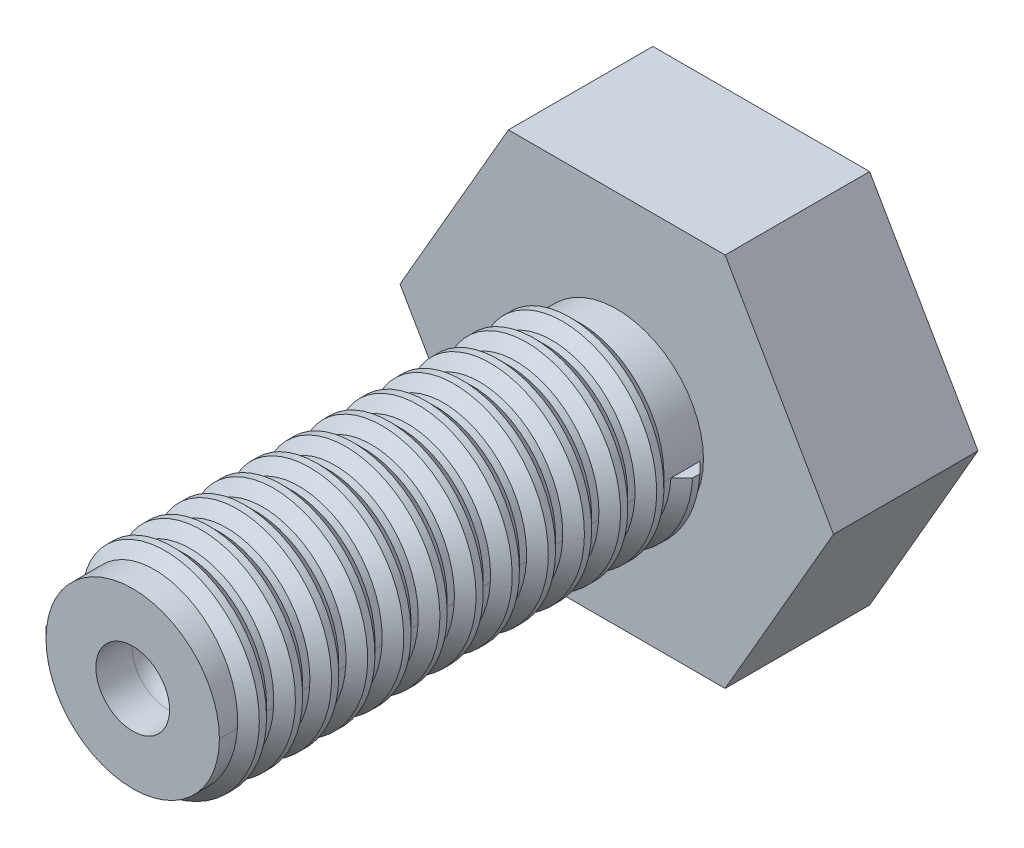
SolidWorks part; units mm, degrees
ref_plane "前视基准面" through (0, 0, 0) normal (0, 0, 1) x (1, 0, 0)
ref_plane "上视基准面" through (0, 0, 0) normal (0, 1, 0) x (1, 0, 0)
ref_plane "右视基准面" through (0, 0, 0) normal (1, 0, 0) x (0, 0, -1)
other "Configuration Table"
sketch "草图1" plane through (0, 0, 0) normal (0, 0, 1) x (1, 0, 0)
  line L13 (15, 0) -> (7.5, 12.9904)
  line L14 (7.5, 12.9904) -> (-7.5, 12.9904)
  line L15 (-7.5, 12.9904) -> (-15, 0)
  line L16 (-15, 0) -> (-7.5, -12.9904)
  line L17 (-7.5, -12.9904) -> (7.5, -12.9904)
  line L18 (7.5, -12.9904) -> (15, 0)
  circle A0 centre (0, 0) radius 15 construction
  dimension "D1" = 30
extrude "凸台-拉伸1" add sketch "草图1" along normal blind 10
sketch "草图2" plane through (0, 0, 10) normal (0, 0, 1) x (1, 0, 0)
  circle A0 centre (0, 0) radius 6
  dimension "D1" = 12
extrude "凸台-拉伸2" add sketch "草图2" along normal blind 33.5
ref_plane "基准面1" through (0, 0, 11.25) normal (0, 0, 1) x (1, 0, 0)
sketch "草图3" plane through (0, 0, 11.25) normal (0, 0, 1) x (1, 0, 0)
  circle A0 centre (0, 0) radius 6 construction
  circle A1 centre (0, 0) radius 6
curve "螺旋线/涡状线1" pitch 2.5 height 31.25 radius 6 left hand yes centre (0, 0, 11.25) axis (0, 0, 1) start towards (1, 0, 0)
sketch "草图4" plane through (0, 0, 0) normal (0, 1, 0) x (1, 0, 0)
  line L0 (6, -10.25) -> (6, -12.25)
  line L1 (6, -12.25) -> (6.75, -11.5)
  line L2 (6.75, -11.5) -> (6.75, -11)
  line L3 (6.75, -11) -> (6, -10.25)
  point P2 (11.7593, -16.009)
  point P5 (12.3627, -16.3346)
  point P6 (6, -11.25)
  dimension "D1" = 0.75
  dimension "D2" = 2
  dimension "D3" = 45
  dimension "D4" = 45
sweep "扫描1" add profiles "草图4" path "螺旋线/涡状线1"
sketch "草图10" plane through (0, 0, 43.5) normal (0, 0, 1) x (1, 0, 0)
  circle A0 centre (0, 0) radius 2.55
  dimension "D1" = 5.1
extrude "切除-拉伸1" cut sketch "草图10" against normal blind 2.5
sketch "草图11" plane through (0, 0, 41) normal (0, 0, 1) x (1, 0, 0)
  line L0 (0, 2.55) -> (0, -2.55)
  arc A3 (0, -2.55) -> (0, 2.55) centre (0, 0) ccw
  dimension "D1" = 5.1
revolve "切除-旋转1" cut sketch "草图11" angle 360 about L0
